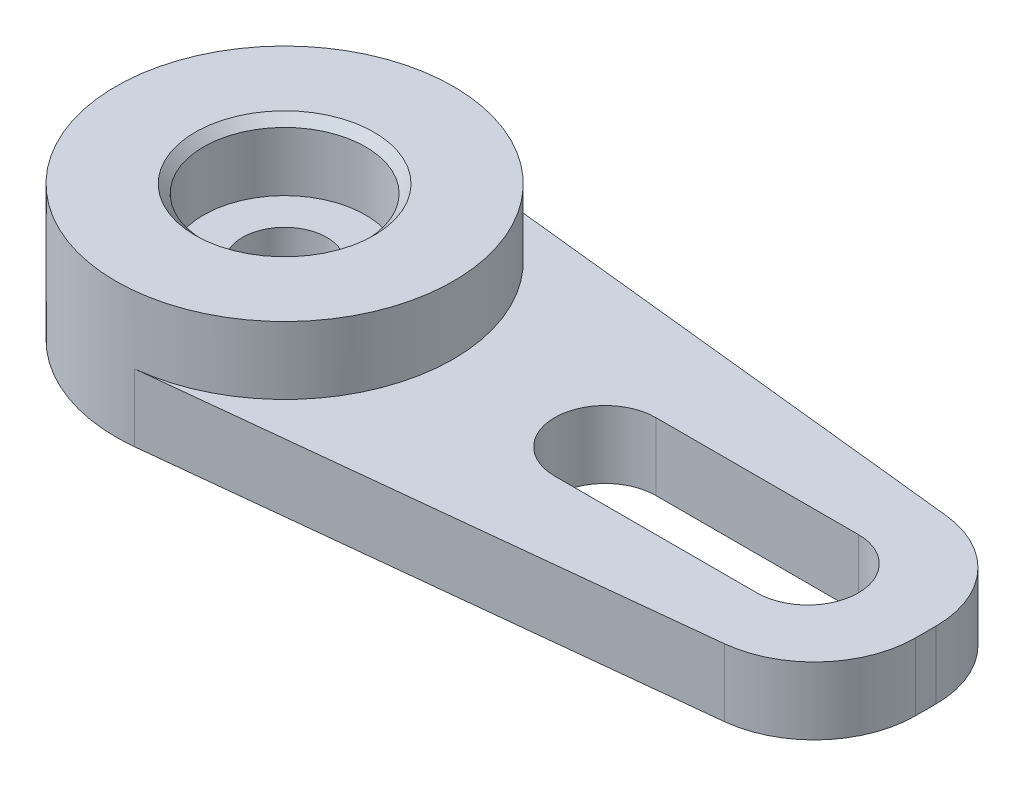
SolidWorks part; units mm, degrees
ref_plane "Front Plane" through (0, 0, 0) normal (0, 0, 1) x (1, 0, 0)
ref_plane "Top Plane" through (0, 0, 0) normal (0, 1, 0) x (1, 0, 0)
ref_plane "Right Plane" through (0, 0, 0) normal (1, 0, 0) x (0, 0, -1)
sketch "Sketch1" plane through (0, 0, 0) normal (0, 1, 0) x (1, 0, 0)
  line L0 (0, 0) -> (19, 0) construction
  line L1 (0.5308, 4.9717) -> (19, 3)
  line L2 (19, 3) -> (19, -3)
  line L3 (0.5308, -4.9717) -> (19, -3)
  circle A0 centre (0, 0) radius 1.25
  circle A1 centre (0, 0) radius 5
  dimension "D1" = 2.5
  dimension "D2" = 10
  dimension "D3" = 6
  dimension "D4" = 19
extrude "Boss-Extrude1" add sketch "Sketch1" along normal blind 2 contours L0 A1 L3 L2 | A1 L0 L2 L1 | A0 A1 region at (3.6133, 0, 3.2481) region at (10.9814, 0, -2.0245) region at (10.9814, 0, 2.0245)
sketch "Sketch2" plane through (0, 2, 0) normal (0, 1, 0) x (1, 0, 0)
  circle A0 centre (0, 0) radius 5
  arc A1 (0.5308, 4.9717) -> (0.5308, -4.9717) centre (0, 0) ccw construction
  circle A4 centre (0, 0) radius 1.25
  circle A5 centre (0, 0) radius 1.25
  dimension "D1" = 0
extrude "Boss-Extrude2" add sketch "Sketch2" along normal blind 2
sketch "Sketch3" plane through (0, 4, 0) normal (0, 1, 0) x (1, 0, 0)
  circle A2 centre (0, 0) radius 2.4
  circle A3 centre (0, 0) radius 2.4
  circle A5 centre (0, 0) radius 1.25
  circle A6 centre (0, 0) radius 1.25
  dimension "D1" = 1.15
  dimension "D2" = 0
extrude "Cut-Extrude1" cut sketch "Sketch3" against normal blind 2
chamfer "Chamfer1" distance 0.25 angle 45 1 edges at (0, 4, 2.4)
sketch "Sketch4" plane through (0, 2, 0) normal (0, 1, 0) x (1, 0, 0)
  line L0 (9.5, 0) -> (15.5, 0) construction
  line L1 (9.5, 1.5) -> (15.5, 1.5)
  line L2 (9.5, -1.5) -> (15.5, -1.5)
  arc A0 (9.5, 1.5) -> (9.5, -1.5) centre (9.5, 0) ccw
  arc A1 (15.5, -1.5) -> (15.5, 1.5) centre (15.5, 0) ccw
  point P2 (12.5, 0)
  dimension "D1" = 6
  dimension "D2" = 3
  dimension "D3" = 12.5
extrude "Cut-Extrude2" cut sketch "Sketch4" against normal blind 3
fillet "Fillet1" radius 3 2 edges at (19, 1, 3) (19, 1, -3)
